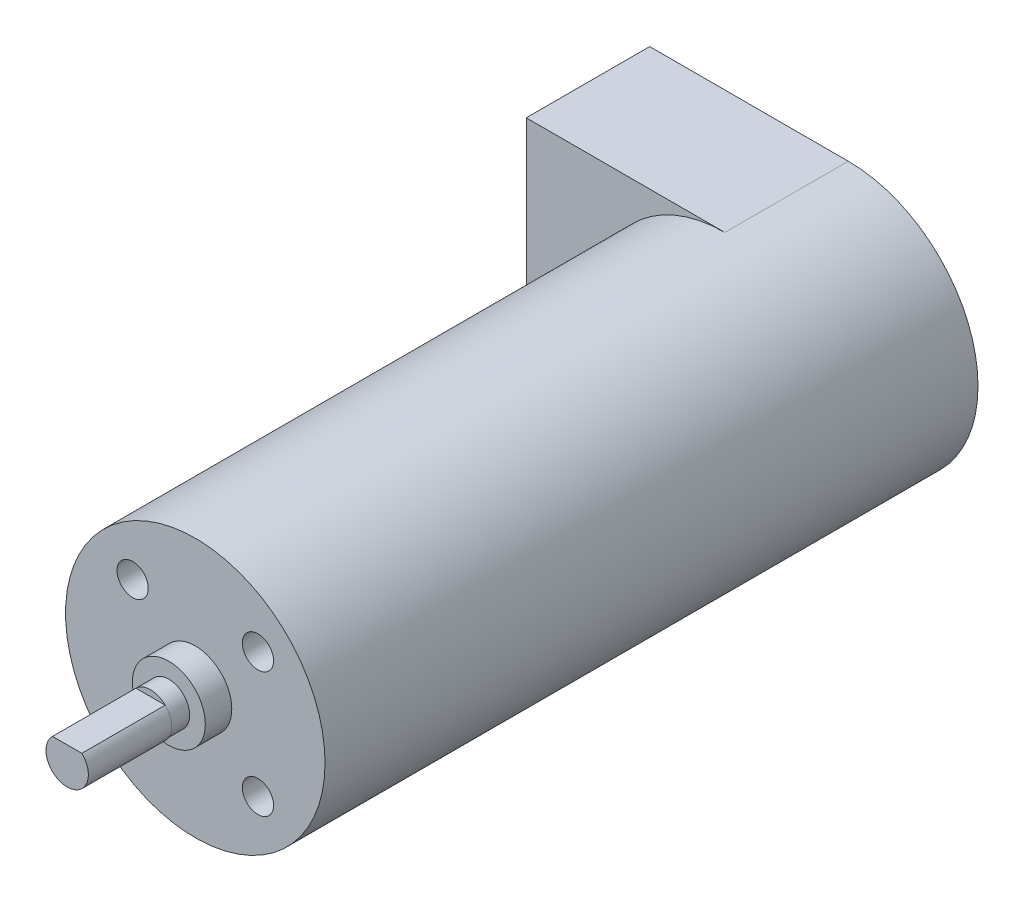
SolidWorks part; units mm, degrees
ref_plane "Front Plane" through (0, 0, 0) normal (0, 0, 1) x (1, 0, 0)
ref_plane "Top Plane" through (0, 0, 0) normal (0, 1, 0) x (1, 0, 0)
ref_plane "Right Plane" through (0, 0, 0) normal (1, 0, 0) x (0, 0, -1)
sketch "Sketch1" plane through (0, 0, 0) normal (0, 0, 1) x (1, 0, 0)
  circle A0 centre (0, 0) radius 12.446
  dimension "D1" = 24.892
extrude "Boss-Extrude1" add sketch "Sketch1" along normal blind 25.4 and the other way blind 25.4
sketch "Sketch2" plane through (0, 0, 25.4) normal (0, 0, 1) x (1, 0, 0)
  circle A0 centre (0, 0) radius 3.5
  dimension "D1" = 7
extrude "Boss-Extrude2" add sketch "Sketch2" along normal blind 2.54
sketch "Sketch4" plane through (0, 0, 27.94) normal (0, 0, 1) x (1, 0, 0)
  circle A0 centre (0, 0) radius 2
  dimension "D1" = 4
extrude "Boss-Extrude3" add sketch "Sketch4" along normal blind 1.75
sketch "Sketch5" plane through (0, 0, 29.69) normal (0, 0, 1) x (1, 0, 0)
  line L0 (1.4056, 1.4228) -> (-1.4056, 1.4228)
  circle A0 centre (0, 0) radius 2 construction
  circle A1 centre (0, 0) radius 2 construction
  arc A2 (-1.4056, 1.4228) -> (1.4056, 1.4228) centre (0, -0.0472) ccw
  dimension "D1" = 1.47
extrude "Boss-Extrude4" add sketch "Sketch5" along normal blind 8
sketch "Sketch6" plane through (0, 0, 25.4) normal (0, 0, 1) x (1, 0, 0)
  line L0 (0, 0) -> (6.0104, 6.0104) construction
  line L1 (0, 0) -> (5.0307, 0) construction
  line L2 (0, 0) -> (0, -1.7575) construction
  circle A0 centre (6.0104, 6.0104) radius 1.5
  circle A1 centre (6.0104, -6.0104) radius 1.5
  circle A2 centre (-6.0104, -6.0104) radius 1.5
  circle A3 centre (-6.0104, 6.0104) radius 1.5
  dimension "D2" = 3
  dimension "D1" = 8.5
extrude "Cut-Extrude1" cut sketch "Sketch6" against normal blind 3.175
sketch "Sketch7" plane through (0, 0, -25.4) normal (0, 0, -1) x (-1, 0, 0)
  line L0 (0, 12.446) -> (19.05, 12.446)
  line L1 (19.05, 12.446) -> (19.05, -12.446)
  line L2 (19.05, -12.446) -> (0, -12.446)
  circle A0 centre (0, 0) radius 12.446 construction
  arc A1 (0, 12.446) -> (0, -12.446) centre (0, 0) ccw
  dimension "D1" = 19.05
  dimension "D2" = 24.892
extrude "Boss-Extrude5" add sketch "Sketch7" along normal blind 11.8364
